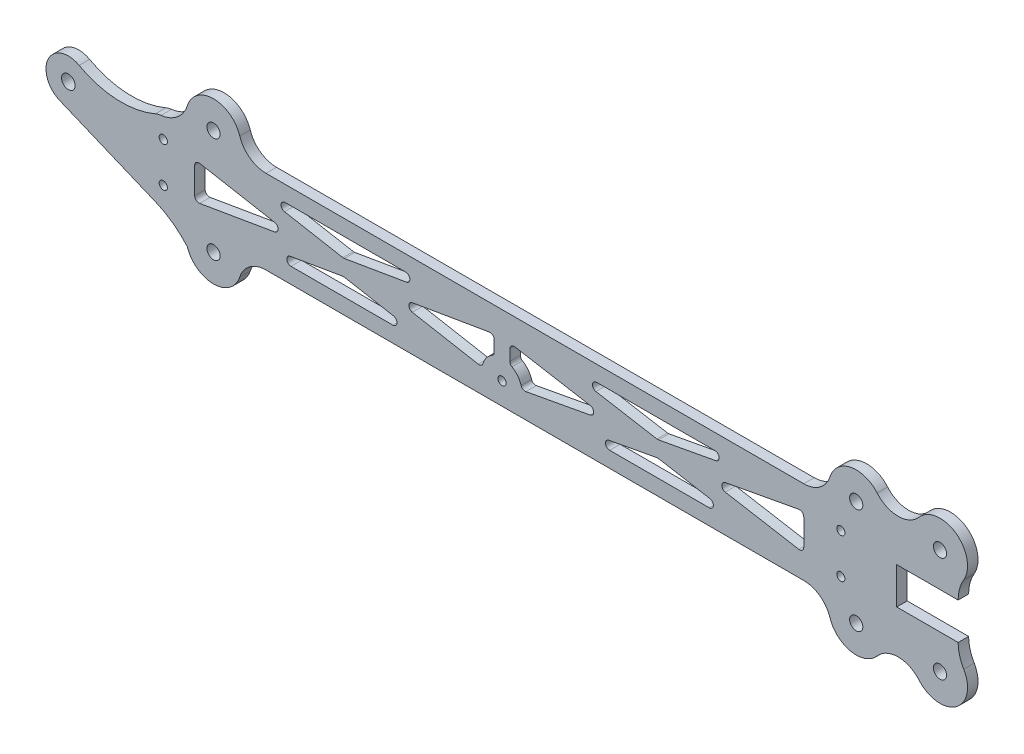
SolidWorks part; units mm, degrees
ref_plane "Front Plane" through (0, 0, 0) normal (0, 0, 1) x (1, 0, 0)
ref_plane "Top Plane" through (0, 0, 0) normal (0, 1, 0) x (1, 0, 0)
ref_plane "Right Plane" through (0, 0, 0) normal (1, 0, 0) x (0, 0, -1)
sketch "Sketch1" plane through (0, 0, 0) normal (0, 0, 1) x (1, 0, 0)
  line L0 (553.1, 14.28) -> (553.1, 5.7479) construction
  line L1 (0, 50.8) -> (69.7828, 50.8)
  line L2 (0, 50.8) -> (0, 0)
  line L3 (0, 0) -> (69.7828, 0)
  line L4 (553.1, 45.0521) -> (553.1, 36.52) construction
  line L5 (515.86, 36.52) -> (553.1, 36.52)
  line L6 (515.86, 36.52) -> (515.86, 14.28)
  line L7 (515.86, 14.28) -> (553.1, 14.28)
  line L8 (101.6, 57.34) -> (101.6, 77.1011) construction
  line L9 (133.4172, 50.8) -> (459.4828, 50.8)
  line L10 (0, 25.4) -> (553.1, 25.4) construction
  line L12 (0, 25.4) -> (457.2, 25.4) construction
  line L13 (133.4172, 0) -> (459.4828, 0)
  line L14 (515.86, 46.34) -> (515.86, 4.46) construction
  line L15 (528.56, 36.52) -> (553.1, 36.52) construction
  line L16 (0, 50.8) -> (553.1, 50.8) construction
  circle A0 centre (13.54, 38.94) radius 4 construction
  circle A1 centre (13.54, 38.94) radius 4.127
  circle A2 centre (101.6, -6.54) radius 4
  arc A3 (133.4172, 0) -> (117.5086, -11.62) centre (133.4172, -16.7) ccw
  arc A4 (69.7828, 0) -> (85.6914, -11.62) centre (69.7828, -16.7) cw
  arc A5 (117.5086, -11.62) -> (85.6914, -11.62) centre (101.6, -6.54) cw
  arc A6 (556.4711, 48.8335) -> (529.4, 68.1844) centre (542.1, 57.34) ccw
  circle A7 centre (71.12, 37.4575) radius 2.4892 construction
  circle A8 centre (13.54, 38.94) radius 11 construction
  circle A12 centre (481.98, 13.3425) radius 2.4892
  circle A13 centre (481.98, 37.4575) radius 2.4892
  circle A14 centre (276.55, 13.3425) radius 2.4892
  circle A15 centre (71.12, 13.3425) radius 2.4892
  circle A16 centre (71.12, 37.4575) radius 2.4892
  circle A17 centre (101.6, 57.34) radius 4
  arc A18 (117.5086, 62.42) -> (85.6914, 62.42) centre (101.6, 57.34) ccw
  arc A19 (69.7828, 50.8) -> (85.6914, 62.42) centre (69.7828, 67.5) ccw
  arc A21 (133.4172, 50.8) -> (117.5086, 62.42) centre (133.4172, 67.5) cw
  circle A22 centre (101.6, 57.34) radius 16.7 construction
  arc A23 (504, 68.1844) -> (475.3914, 62.42) centre (491.3, 57.34) ccw
  circle A24 centre (491.3, 57.34) radius 4
  circle A25 centre (542.1, 57.34) radius 4
  arc A27 (556.4711, 1.9665) -> (529.4, -17.3844) centre (542.1, -6.54) cw
  circle A28 centre (542.1, -6.54) radius 4
  circle A29 centre (491.3, -6.54) radius 4
  arc A30 (504, -17.3844) -> (475.3914, -11.62) centre (491.3, -6.54) cw
  arc A31 (504, 68.1844) -> (529.4, 68.1844) centre (516.7, 79.0287) ccw
  arc A32 (504, -17.3844) -> (529.4, -17.3844) centre (516.7, -28.2287) cw
  arc A33 (459.4828, 50.8) -> (475.3914, 62.42) centre (459.4828, 67.5) ccw
  arc A34 (459.4828, 0) -> (475.3914, -11.62) centre (459.4828, -16.7) cw
  arc A35 (553.1, 36.52) -> (556.4711, 48.8335) centre (577.2739, 36.52) cw
  arc A36 (553.1, 14.28) -> (556.4711, 1.9665) centre (577.2739, 14.28) ccw
  dimension "D1" = 8
  dimension "D3" = 8
  dimension "D2" = 0.127
  dimension "D4" = 12.7
extrude "Boss-Extrude1" add sketch "Sketch1" along normal blind 6.35
sketch "Sketch2" plane through (0, 0, 0) normal (0, 0, -1) x (-1, 0, 0)
  line L0 (-459.4828, 41.275) -> (-459.4828, 9.525)
  line L1 (-459.4828, 9.525) -> (-287.9416, 9.525)
  line L2 (-90.17, 9.525) -> (-90.17, 41.275)
  line L3 (-90.17, 41.275) -> (-459.4828, 41.275)
  line L4 (-459.4828, 50.8) -> (-133.4172, 50.8) construction
  line L5 (-133.4172, 0) -> (-459.4828, 0) construction
  line L6 (-459.4828, 50.8) -> (-133.4172, 50.8) construction
  line L7 (-459.4828, 50.8) -> (-459.4828, 0) construction
  line L8 (-265.1584, 9.525) -> (-90.17, 9.525)
  line L9 (-459.4828, 41.275) -> (-287.9416, 9.525) construction
  line L10 (-458.616, 45.958) -> (-287.0748, 14.208)
  line L11 (-276.55, 13.3425) -> (-276.55, 41.275) construction
  line L12 (-460.3496, 36.592) -> (-288.8083, 4.842)
  line L13 (-459.4828, 9.525) -> (-276.55, 41.275) construction
  line L14 (-460.2972, 14.2173) -> (-277.3644, 45.9673)
  line L15 (-458.6684, 4.8327) -> (-275.7356, 36.5827)
  line L16 (-276.55, 41.275) -> (-90.17, 9.525) construction
  line L17 (-275.7502, 45.9699) -> (-89.3702, 14.2199)
  line L18 (-277.3498, 36.5801) -> (-90.9698, 4.8301)
  line L19 (-265.1584, 9.525) -> (-90.17, 41.275) construction
  line L20 (-266.0087, 14.211) -> (-91.0202, 45.961)
  line L21 (-264.3082, 4.839) -> (-89.3198, 36.589)
  line L22 (-276.55, 41.275) -> (-276.55, 13.3425) construction
  line L23 (-271.7875, 41.275) -> (-271.7875, 13.3425)
  line L24 (-281.3125, 41.275) -> (-281.3125, 13.3425)
  line L25 (-71.12, 37.4575) -> (-71.12, 18.7215) construction
  arc A0 (-458.616, 45.958) -> (-460.3496, 36.592) centre (-459.4828, 41.275) ccw
  arc A1 (-288.8083, 4.842) -> (-287.0748, 14.208) centre (-287.9416, 9.525) ccw
  arc A2 (-460.2972, 14.2173) -> (-458.6684, 4.8327) centre (-459.4828, 9.525) ccw
  circle A3 centre (-276.55, 13.3425) radius 12.0142
  arc A4 (-265.1584, 9.525) -> (-287.9416, 9.525) centre (-276.55, 13.3425) ccw
  arc A5 (-275.7356, 36.5827) -> (-277.3644, 45.9673) centre (-276.55, 41.275) ccw
  arc A6 (-275.7502, 45.9699) -> (-277.3498, 36.5801) centre (-276.55, 41.275) ccw
  arc A7 (-90.9698, 4.8301) -> (-89.3702, 14.2199) centre (-90.17, 9.525) ccw
  arc A8 (-266.0087, 14.211) -> (-264.3082, 4.839) centre (-265.1584, 9.525) ccw
  arc A9 (-89.3198, 36.589) -> (-91.0202, 45.961) centre (-90.17, 41.275) ccw
  arc A10 (-271.7875, 41.275) -> (-281.3125, 41.275) centre (-276.55, 41.275) ccw
  arc A11 (-281.3125, 13.3425) -> (-271.7875, 13.3425) centre (-276.55, 13.3425) ccw
  circle A12 centre (-71.12, 37.4575) radius 2.4892 construction
  circle A13 centre (-71.12, 37.4575) radius 2.4892 construction
  point P11 (-373.7122, 25.4)
  point P19 (-368.0164, 25.4)
  point P24 (-183.36, 25.4)
  point P30 (-177.6642, 25.4)
  point P36 (-276.55, 27.3088)
  dimension "D4" = 4.7625
  dimension "D1" = 9.525
  dimension "D2" = 9.525
  dimension "D5" = 19.05
  dimension "D3" = 9.525
extrude "Cut-Extrude1" cut sketch "Sketch2" against normal through all contours L0 L14 L12 | L10 L14 L3 | A4 L24 L15 L10 | L15 L1 L12 | A4 L20 L18 L23 | L17 L20 L3 | L21 L17 L2 | L21 L8 L18 region at (438.9679, 25.2769, 0) region at (369.5478, 37.4261, 0) region at (372.2418, 13.0338, 0) region at (303.7071, 25.0443, 0) region at (181.8285, 37.4284, 0) region at (248.9883, 25.0507, 0) region at (111.0902, 25.2794, 0) region at (179.1359, 13.038, 0)
fillet "Fillet1" radius 2.54 26 edges at (180.3963, 20.064, 3.175) (118.5297, 9.525, 3.175) (238.4816, 9.525, 3.175) (288.5108, 14.4738, 3.175) (343.9737, 24.7392, 3.175) (207.9141, 24.7517, 3.175) (264.5887, 14.4686, 3.175) (459.4828, 14.3587, 3.175) (459.4828, 36.4316, 3.175) (116.8468, 41.275, 3.175) (180.4483, 29.7351, 3.175) (248.1903, 41.275, 3.175) (90.17, 36.4347, 3.175) (90.17, 14.3561, 3.175) (152.9306, 25.0474, 3.175) (304.4001, 41.275, 3.175) (370.9288, 29.7282, 3.175) (433.3146, 41.275, 3.175) (370.9828, 20.0514, 3.175) (314.1098, 9.525, 3.175) (431.6327, 9.525, 3.175) (397.938, 25.0405, 3.175) (271.7875, 24.3724, 3.175) (271.7875, 35.6326, 3.175) (281.3125, 35.6147, 3.175) (281.3125, 24.3724, 3.175)
sketch "Sketch4" plane through (0, 0, 6.35) normal (0, 0, 1) x (1, 0, 0)
  line L0 (66.5068, 2.2493) -> (8.3409, 26.4379)
  line L1 (0, 50.8) -> (7.0076, 50.8)
  line L2 (69.7828, 50.8) -> (0, 50.8) construction
  line L3 (0, 50.8) -> (0, 0) construction
  line L4 (69.7828, 50.8) -> (0, 50.8)
  line L5 (0, 0) -> (69.7828, 0) construction
  line L6 (0, 0) -> (69.7828, 0)
  line L7 (0, 50.8) -> (0, 0)
  circle A2 centre (13.54, 38.94) radius 4.127 construction
  circle A3 centre (13.54, 38.94) radius 13.54
  circle A12 centre (71.12, 37.4575) radius 12.0142
  circle A13 centre (71.12, 37.4575) radius 12.0142
  arc A14 (66.5068, 2.2493) -> (85.6914, -11.62) centre (46.7276, -45.3133) cw
  circle A15 centre (71.12, 13.3425) radius 12.0142
  circle A16 centre (71.12, 13.3425) radius 12.0142
  arc A17 (85.6914, -11.62) -> (69.7828, 0) centre (69.7828, -16.7) ccw construction
  arc A19 (20.0724, 50.8) -> (66.3934, 48.5029) centre (45.5871, 97.1238) ccw
  arc A20 (69.792, 49.3981) -> (85.6914, 62.42) centre (67.7051, 68.1635) ccw
  arc A21 (117.5086, 62.42) -> (85.6914, 62.42) centre (101.6, 57.34) ccw construction
  arc A22 (69.7828, 50.8) -> (85.6914, 62.42) centre (69.7828, 67.5) ccw construction
  arc A23 (69.7828, 50.8) -> (85.6914, 62.42) centre (69.7828, 67.5) ccw
  arc A24 (85.6914, -11.62) -> (69.7828, 0) centre (69.7828, -16.7) ccw
  point P37 (0, 0)
  dimension "D2" = 9.525
  dimension "D3" = 9.525
extrude "Boss-Extrude2" add sketch "Sketch4" against normal up to surface (6.35 mm away) contours L4 A3 | A14 A24 region at (79.4311, -4.7257, 6.35) region at (13.54, 51.4757, 6.35) up to face at (370.1526, 35.8346, 0)
extrude "Cut-Extrude2" cut sketch "Sketch4<3>" against normal through all contours A3 L1 L7 | A24 A14 L0 A3 L7 L6 | A23 L4 A19 A13 A20 region at (23.6557, 10.2534, 6.35) region at (46.9166, 48.3164, 6.35) region at (1.9591, 48.0096, 6.35)
sketch "Sketch4<3>" plane through (0, 0, 6.35) normal (0, 0, 1) x (1, 0, 0) same geometry as "Sketch4"
